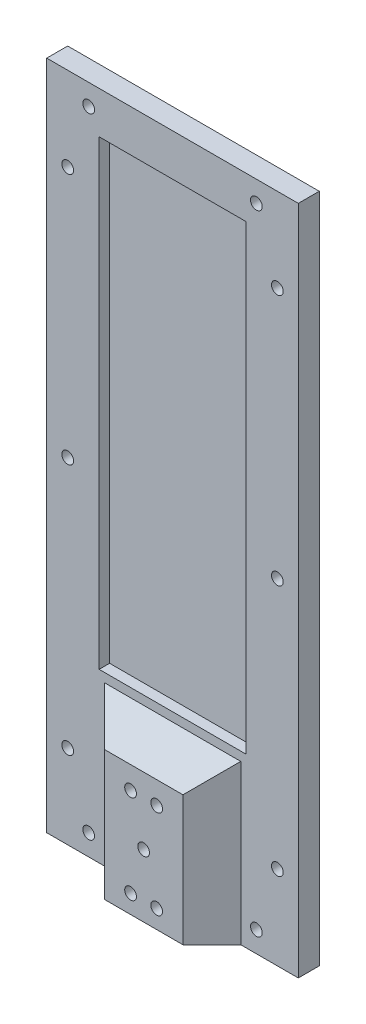
SolidWorks part; units mm, degrees
material "Copper"
ref_plane "Front Plane" through (0, 0, 0) normal (0, 0, 1) x (1, 0, 0)
ref_plane "Top Plane" through (0, 0, 0) normal (0, 1, 0) x (1, 0, 0)
ref_plane "Right Plane" through (0, 0, 0) normal (1, 0, 0) x (0, 0, -1)
sketch "Sketch1" plane through (0, 0, 0) normal (0, 0, 1) x (1, 0, 0)
  line L1 (0, 0) -> (76.2, 0)
  line L2 (0, 0) -> (0, 203.2)
  line L3 (0, 203.2) -> (76.2, 203.2)
  line L4 (76.2, 0) -> (76.2, 203.2)
  dimension "D1" = 76.2
  dimension "D2" = 203.2
extrude "Boss-Extrude1" add sketch "Sketch1" along normal blind 6.35
sketch "Sketch6" plane through (0, 0, 0) normal (0, 0, -1) x (-1, 0, 0)
  line L0 (0, 0) -> (-76.2, 0) construction
  line L1 (-76.2, 0) -> (-76.2, 203.2) construction
  line L2 (-76.2, 203.2) -> (0, 203.2) construction
  line L3 (0, 203.2) -> (0, 0) construction
  circle A0 centre (-63.5, 6.35) radius 1.778
  circle A1 centre (-12.7, 6.35) radius 1.778
  circle A2 centre (-6.35, 177.8) radius 1.778
  circle A3 centre (-6.35, 25.4) radius 1.778
  circle A4 centre (-69.85, 25.4) radius 1.778
  circle A5 centre (-69.85, 177.8) radius 1.778
  circle A6 centre (-63.5, 196.85) radius 1.778
  circle A7 centre (-12.7, 196.85) radius 1.778
  circle A8 centre (-6.35, 101.6) radius 1.778
  circle A9 centre (-69.85, 101.6) radius 1.778
  dimension "D1" = 3.556
  dimension "D4" = 50.8
  dimension "D5" = 12.7
  dimension "D6" = 6.35
  dimension "D8" = 50.8
  dimension "D9" = 12.7
  dimension "D11" = 6.35
  dimension "D16" = 152.4
  dimension "D17" = 25.4
  dimension "D18" = 3.556
  dimension "D19" = 3.556
  dimension "D2" = 6.35
  dimension "D3" = 6.35
  dimension "D7" = 6.35
  dimension "D10" = 6.35
  dimension "D12" = 152.4
  dimension "D13" = 25.4
  dimension "D14" = 6.35
  dimension "D15" = 6.35
  dimension "D20" = 6.35
  dimension "D21" = 6.35
  dimension "D22" = 76.2
  dimension "D23" = 76.2
extrude "Cut-Extrude4" cut sketch "Sketch6" against normal blind 6.35
sketch "Sketch7" plane through (0, 0, 6.35) normal (0, 0, 1) x (1, 0, 0)
  line L0 (0, 0) -> (76.2, 0) construction
  line L1 (27.432, 0) -> (48.768, 0)
  line L2 (27.432, 0) -> (27.432, 38.1)
  line L3 (27.432, 38.1) -> (48.768, 38.1)
  line L4 (48.768, 0) -> (48.768, 38.1)
  line L5 (76.2, 0) -> (76.2, 203.2) construction
  dimension "D1" = 21.336
  dimension "D2" = 38.1
  dimension "D3" = 27.432
extrude "Boss-Extrude2" add sketch "Sketch7" along normal blind 8.7546
sketch "Sketch8" plane through (0, 0, 15.1046) normal (0, 0, 1) x (1, 0, 0)
  line L0 (27.432, 19.05) -> (48.768, 19.05) construction
  line L1 (27.432, 38.1) -> (27.432, 0) construction
  line L2 (48.768, 0) -> (48.768, 38.1) construction
  line L3 (38.1, 38.1) -> (38.1, 0)
  line L4 (48.768, 38.1) -> (27.432, 38.1) construction
  line L5 (27.432, 0) -> (48.768, 0) construction
  circle A0 centre (34.1503, 32.5247) radius 1.778
  circle A1 centre (42.0497, 32.5247) radius 1.778
  circle A2 centre (34.1503, 5.5753) radius 1.778
  circle A3 centre (42.0497, 5.5753) radius 1.778
  circle A4 centre (38.1, 19.05) radius 1.778
  dimension "D1" = 3.556
  dimension "D2" = 7.8994
  dimension "D3" = 7.8994
  dimension "D6" = 13.4747
  dimension "D7" = 13.4747
  dimension "D10" = 3.556
  dimension "D4" = 26.9494
  dimension "D5" = 26.9494
  dimension "D8" = 3.9497
  dimension "D9" = 3.9497
extrude "Cut-Extrude5" cut sketch "Sketch8" against normal through all contours A2 | A3 | A1 | A0 | A4 region at (34.1503, 32.5247, 15.1046) region at (42.0497, 32.5247, 15.1046) region at (34.1503, 5.5753, 15.1046) region at (42.0497, 5.5753, 15.1046)
sketch "Sketch9" plane through (0, 0, 6.35) normal (0, 0, 1) x (1, 0, 0)
  line L0 (0, 203.2) -> (0, 0) construction
  line L1 (15.875, 190.5) -> (60.325, 190.5)
  line L2 (15.875, 190.5) -> (15.875, 50.8)
  line L3 (15.875, 50.8) -> (60.325, 50.8)
  line L4 (60.325, 190.5) -> (60.325, 50.8)
  line L5 (76.2, 203.2) -> (0, 203.2) construction
  dimension "D1" = 139.7
  dimension "D2" = 44.45
  dimension "D3" = 15.875
  dimension "D4" = 12.7
extrude "Cut-Extrude6" cut sketch "Sketch9" against normal blind 3.175
chamfer "Chamfer1" distance 10 angle 45 3 edges at (27.432, 19.05, 6.35) (38.1, 38.1, 6.35) (48.768, 19.05, 6.35)
